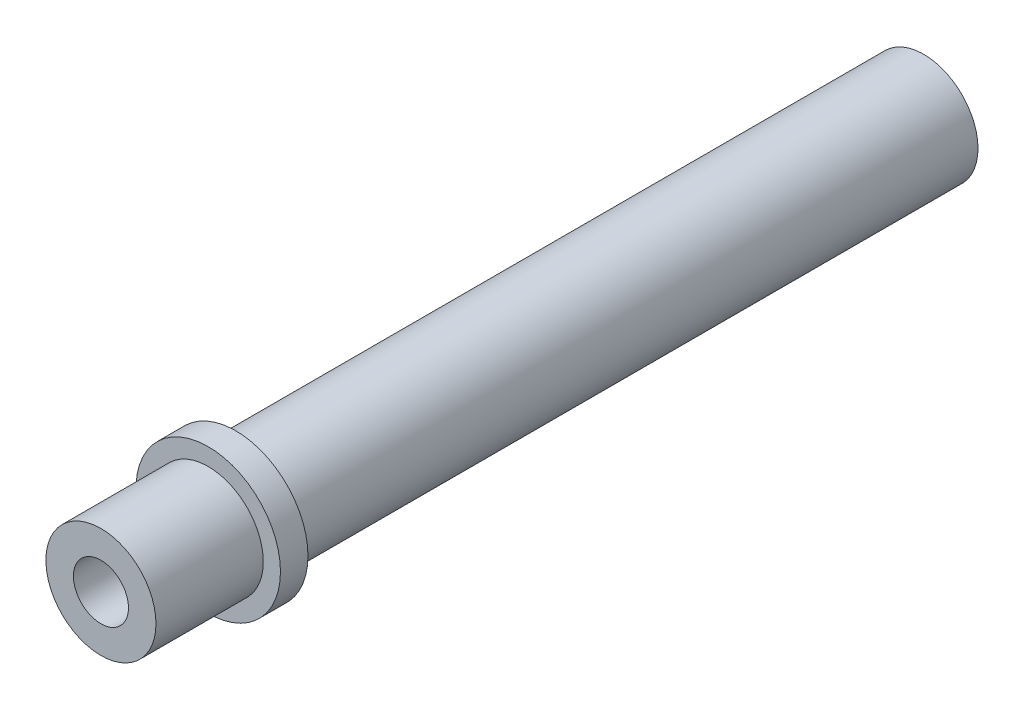
SolidWorks part; units mm, degrees
ref_plane "Front Plane" through (0, 0, 0) normal (0, 0, 1) x (1, 0, 0)
ref_plane "Top Plane" through (0, 0, 0) normal (0, 1, 0) x (1, 0, 0)
ref_plane "Right Plane" through (0, 0, 0) normal (1, 0, 0) x (0, 0, -1)
sketch "S01 - Printable sliding pin - 7.90 mm" plane through (0, 0, 0) normal (0, 0, 1) x (1, 0, 0)
  circle A0 centre (0, 0) radius 3.95
extrude "01 - Printable sliding pin - 7.90 mm" add sketch "S01 - Printable sliding pin - 7.90 mm" along normal blind 40
sketch "S02 - Recessed load shoulder" plane through (0, 0, 0) normal (0, 0, 1) x (1, 0, 0)
  circle A0 centre (0, 0) radius 5.25
extrude "02 - Recessed load shoulder" add sketch "S02 - Recessed load shoulder" along normal blind 2 from offset 40
sketch "S03 - Locating pilot through swing arm" plane through (0, 0, 0) normal (0, 0, 1) x (1, 0, 0)
  circle A0 centre (0, 0) radius 4
extrude "03 - Locating pilot through swing arm" add sketch "S03 - Locating pilot through swing arm" along normal blind 7.8 from offset 42
sketch "S04 - M3 heat-set pocket in supported root" plane through (0, 0, 0) normal (0, 0, 1) x (1, 0, 0)
  circle A0 centre (0, 0) radius 2
extrude "04 - M3 heat-set pocket in supported root" cut sketch "S04 - M3 heat-set pocket in supported root" along normal blind 7.3 from offset 42.6
sketch "S01 - Extended sliding journal - 10 mm" plane through (0, 0, 0) normal (0, 0, 1) x (1, 0, 0)
  circle A0 centre (0, 0) radius 3.95
extrude "01 - Extended sliding journal - 10 mm" add sketch "S01 - Extended sliding journal - 10 mm" along normal blind 10.05 from offset 10 offset against normal yes
